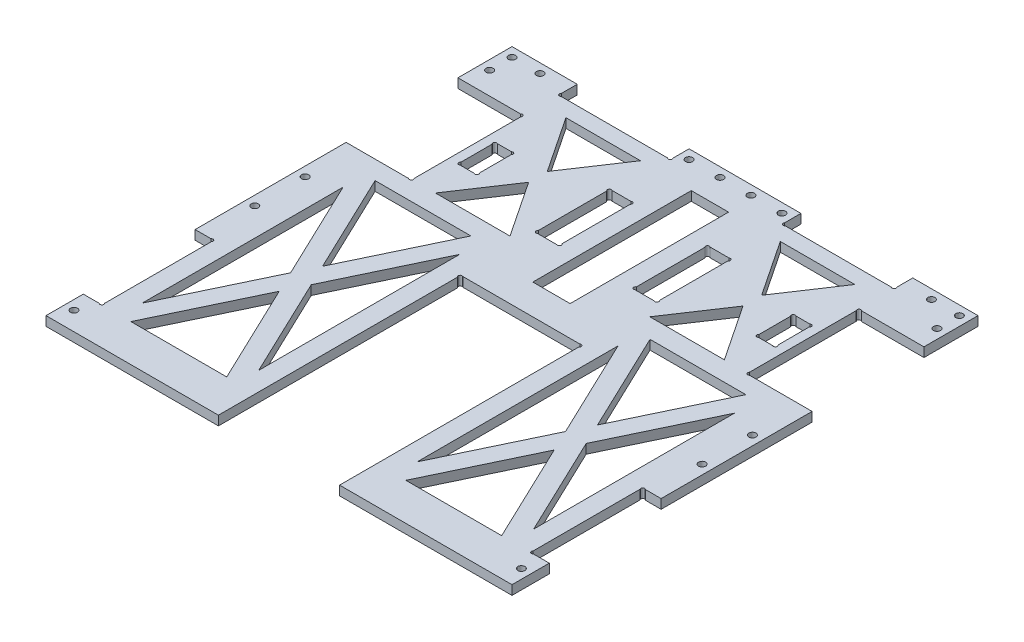
SolidWorks part; units mm, degrees
material "7050-T73510"
ref_plane "Front Plane" through (0, 0, 0) normal (0, 0, 1) x (1, 0, 0)
ref_plane "Top Plane" through (0, 0, 0) normal (0, 1, 0) x (1, 0, 0)
ref_plane "Right Plane" through (0, 0, 0) normal (1, 0, 0) x (0, 0, -1)
sketch "Sketch1" plane through (0, 0, 0) normal (0, 1, 0) x (1, 0, 0)
  line L0 (0, -55) -> (0, 55) construction
  line L1 (-158.75, -76.2) -> (158.75, -76.2)
  line L2 (-158.75, -76.2) -> (-158.75, 76.2)
  line L3 (-158.75, 76.2) -> (158.75, 76.2)
  line L4 (158.75, -76.2) -> (158.75, 76.2)
  line L5 (-158.75, -76.2) -> (158.75, 76.2) construction
  line L6 (-158.75, 76.2) -> (158.75, -76.2) construction
  line L7 (-158.75, -76.2) -> (-25.4, -76.2)
  line L8 (-158.75, -76.2) -> (-158.75, -241.3)
  line L9 (-158.75, -241.3) -> (-25.4, -241.3)
  line L10 (-25.4, -76.2) -> (-25.4, -241.3)
  line L11 (25.4, -76.2) -> (25.4, -241.3)
  line L12 (158.75, -241.3) -> (25.4, -241.3)
  line L13 (158.75, -76.2) -> (158.75, -241.3)
  line L14 (158.75, -76.2) -> (25.4, -76.2)
  line L15 (-41.275, -76.2) -> (-41.275, -241.3)
  line L16 (41.275, -76.2) -> (41.275, -241.3)
  point P0 (0, 0)
  dimension "D1" = 317.5
  dimension "D2" = 152.4
  dimension "D3" = 317.5
  dimension "D4" = 50.8
  dimension "D5" = 15.875
extrude "Boss-Extrude1" add sketch "Sketch1" along normal blind 6.35 contours L15 L1 L8 L9 | L14 L16 L12 L13 | L1 L7 L14 L4 L3 L2 region at (0, 0, 0) region at (-100.0125, 0, 158.75) region at (100.0125, 0, 158.75)
sketch "Sketch2" plane through (0, 6.35, 0) normal (0, 1, 0) x (1, 0, 0)
  line L0 (158.75, -241.3) -> (158.75, 76.2) construction
  line L1 (158.75, 39.37) -> (114.3, 39.37)
  line L2 (158.75, 39.37) -> (158.75, -36.83)
  line L3 (158.75, -36.83) -> (114.3, -36.83)
  line L4 (114.3, 39.37) -> (114.3, -36.83)
  line L5 (-158.75, 76.2) -> (158.75, 76.2) construction
  line L6 (158.75, -139.7) -> (146.05, -139.7)
  line L7 (158.75, -139.7) -> (158.75, -215.9)
  line L8 (158.75, -215.9) -> (146.05, -215.9)
  line L9 (146.05, -139.7) -> (146.05, -215.9)
  line L10 (0, -3.4925) -> (0, 3.4925) construction
  line L11 (-158.75, -215.9) -> (-146.05, -215.9)
  line L12 (-146.05, -139.7) -> (-146.05, -215.9)
  line L13 (-158.75, -139.7) -> (-146.05, -139.7)
  line L14 (-158.75, -139.7) -> (-158.75, -215.9)
  line L15 (-158.75, -36.83) -> (-114.3, -36.83)
  line L16 (-114.3, 39.37) -> (-114.3, -36.83)
  line L17 (-158.75, 39.37) -> (-114.3, 39.37)
  line L18 (-158.75, 39.37) -> (-158.75, -36.83)
  line L19 (-114.3, 63.5) -> (-38.1, 63.5)
  line L20 (114.3, 76.2) -> (38.1, 76.2)
  line L21 (114.3, 76.2) -> (114.3, 63.5)
  line L22 (114.3, 63.5) -> (38.1, 63.5)
  line L23 (38.1, 76.2) -> (38.1, 63.5)
  line L24 (-38.1, 76.2) -> (-38.1, 63.5)
  line L25 (-114.3, 76.2) -> (-38.1, 76.2)
  line L26 (-114.3, 76.2) -> (-114.3, 63.5)
  point P30 (0, 0)
  dimension "D1" = 44.45
  dimension "D2" = 12.7
  dimension "D3" = 76.2
  dimension "D4" = 76.2
  dimension "D5" = 36.83
  dimension "D6" = 215.9
  dimension "D7" = 76.2
  dimension "D8" = 12.7
  dimension "D9" = 76.2
extrude "Cut-Extrude1" cut sketch "Sketch2" against normal through all
sketch "Sketch4" plane through (0, 6.35, 0) normal (0, 1, 0) x (1, 0, 0)
  line L0 (41.275, -76.2) -> (41.275, -241.3) construction
  line L1 (53.975, -215.9) -> (133.35, -215.9)
  line L2 (53.975, -215.9) -> (53.975, -49.53)
  line L3 (53.975, -49.53) -> (133.35, -49.53)
  line L4 (133.35, -215.9) -> (133.35, -49.53)
  line L5 (146.05, -139.7) -> (146.05, -215.9) construction
  line L6 (158.75, -241.3) -> (41.275, -241.3) construction
  line L7 (53.975, -215.9) -> (133.35, -49.53) construction
  line L8 (53.975, -49.53) -> (133.35, -215.9) construction
  line L9 (133.35, -201.1532) -> (61.0107, -49.53)
  line L10 (126.3143, -215.9) -> (53.975, -64.2768)
  line L11 (53.975, -201.1532) -> (126.3143, -49.53)
  line L12 (61.0107, -215.9) -> (133.35, -64.2768)
  line L13 (114.3, -36.83) -> (158.75, -36.83) construction
  line L14 (0, -3.4925) -> (0, 3.4925) construction
  line L15 (-53.975, -201.1532) -> (-126.3143, -49.53)
  line L16 (-126.3143, -215.9) -> (-53.975, -64.2768)
  line L17 (-133.35, -201.1532) -> (-61.0107, -49.53)
  line L18 (-61.0107, -215.9) -> (-133.35, -64.2768)
  line L19 (-53.975, -49.53) -> (-133.35, -49.53)
  line L20 (-133.35, -215.9) -> (-133.35, -49.53)
  line L21 (-53.975, -215.9) -> (-133.35, -215.9)
  line L22 (-53.975, -215.9) -> (-53.975, -49.53)
  point P18 (116.9135, -166.7022)
  dimension "D1" = 12.7
  dimension "D2" = 12.7
  dimension "D3" = 25.4
  dimension "D4" = 12.7
  dimension "D5" = 12.7
extrude "Cut-Extrude3" cut sketch "Sketch4" against normal through all contours L12 L9 L4 | L12 L1 L10 | L2 L11 L10 | L9 L11 L3 | L21 L18 L16 | L20 L17 L18 | L17 L19 L15 | L15 L22 L16 region at (93.6625, 6.35, 193.0873) region at (64.8589, 6.35, 132.715) region at (122.4661, 6.35, 132.715) region at (93.6625, 6.35, 72.3427) region at (-64.8589, 6.35, 132.715) region at (-93.6625, 6.35, 72.3427) region at (-93.6625, 6.35, 193.0873) region at (-122.4661, 6.35, 132.715)
sketch "Sketch3" plane through (0, 6.35, 0) normal (0, 1, 0) x (1, 0, 0)
  line L0 (-41.275, -76.2) -> (41.275, -76.2) construction
  line L1 (-41.275, -25.4) -> (-25.4, -25.4)
  line L2 (-41.275, -25.4) -> (-41.275, 25.4)
  line L3 (-41.275, 25.4) -> (-25.4, 25.4)
  line L4 (-25.4, -25.4) -> (-25.4, 25.4)
  line L5 (0, -3.4925) -> (0, 3.4925) construction
  line L6 (41.275, 25.4) -> (25.4, 25.4)
  line L7 (25.4, -25.4) -> (25.4, 25.4)
  line L8 (41.275, -25.4) -> (25.4, -25.4)
  line L9 (41.275, -25.4) -> (41.275, 25.4)
  line L10 (114.3, 39.37) -> (114.3, -36.83) construction
  line L11 (95.25, 13.97) -> (107.95, 13.97)
  line L12 (95.25, 13.97) -> (95.25, -11.43)
  line L13 (95.25, -11.43) -> (107.95, -11.43)
  line L14 (107.95, 13.97) -> (107.95, -11.43)
  line L15 (38.1, 63.5) -> (114.3, 63.5) construction
  line L16 (-95.25, -11.43) -> (-107.95, -11.43)
  line L17 (-107.95, 13.97) -> (-107.95, -11.43)
  line L18 (-95.25, 13.97) -> (-107.95, 13.97)
  line L19 (-95.25, 13.97) -> (-95.25, -11.43)
  dimension "D1" = 50.8
  dimension "D2" = 15.875
  dimension "D3" = 50.8
  dimension "D4" = 50.8
  dimension "D5" = 25.4
  dimension "D6" = 12.7
  dimension "D7" = 6.35
  dimension "D8" = 49.53
extrude "Cut-Extrude2" cut sketch "Sketch3" against normal through all
sketch "Sketch6" plane through (0, 6.35, 0) normal (0, 1, 0) x (1, 0, 0)
  line L0 (-25.4, -25.4) -> (-25.4, 25.4) construction
  line L1 (-19.05, 63.5) -> (19.05, 63.5)
  line L2 (-19.05, 63.5) -> (-19.05, -63.5)
  line L3 (-19.05, -63.5) -> (19.05, -63.5)
  line L4 (19.05, 63.5) -> (19.05, -63.5)
  line L5 (25.4, 25.4) -> (25.4, -25.4) construction
  line L6 (-38.1, 76.2) -> (38.1, 76.2) construction
  line L7 (-41.275, -76.2) -> (41.275, -76.2) construction
  line L8 (-19.05, -63.5) -> (19.05, 63.5) construction
  line L9 (19.05, -63.5) -> (-19.05, 63.5) construction
  line L10 (12.4204, -63.5) -> (-19.05, 41.4014)
  line L11 (-12.4204, 63.5) -> (19.05, -41.4014)
  line L12 (-19.05, -41.4014) -> (12.4204, 63.5)
  line L13 (19.05, 41.4014) -> (-12.4204, -63.5)
  dimension "D1" = 6.35
  dimension "D2" = 6.35
  dimension "D3" = 12.7
  dimension "D4" = 12.7
  dimension "D5" = 12.7
  dimension "D6" = 12.7
extrude "Cut-Extrude5" [suppressed] cut sketch "Sketch6" against normal through all contours L10 L13 L3 | L4 L13 L11 | L2 L12 L10 | L11 L12 L1
sketch "Sketch7" plane through (0, 6.35, 0) normal (0, 1, 0) x (1, 0, 0)
  line L0 (158.75, -139.7) -> (146.05, -139.7) construction
  line L1 (158.75, -139.7) -> (158.75, -36.83) construction
  line L2 (0, -3.4925) -> (0, 3.4925) construction
  line L3 (158.75, -241.3) -> (41.275, -241.3) construction
  line L4 (-38.1, 76.2) -> (-38.1, 63.5) construction
  line L5 (114.3, 76.2) -> (158.75, 76.2) construction
  line L6 (-38.1, 76.2) -> (38.1, 76.2) construction
  circle A0 centre (152.4, -105.41) radius 2.413
  circle A1 centre (152.4, -71.12) radius 2.413
  circle A8 centre (152.4, -228.6) radius 2.413
  circle A9 centre (152.4, 69.85) radius 2.413
  circle A10 centre (133.35, 69.85) radius 2.413
  circle A12 centre (152.4, 54.61) radius 2.413
  circle A19 centre (-152.4, -228.6) radius 2.413
  circle A20 centre (-31.75, 69.85) radius 2.413
  circle A21 centre (-10.668, 69.85) radius 2.413
  circle A22 centre (10.414, 69.85) radius 2.413
  circle A23 centre (31.496, 69.85) radius 2.413
  circle A24 centre (-152.4, 54.61) radius 2.413
  circle A25 centre (-133.35, 69.85) radius 2.413
  circle A26 centre (-152.4, 69.85) radius 2.413
  circle A27 centre (-152.4, -71.12) radius 2.413
  circle A28 centre (-152.4, -105.41) radius 2.413
  dimension "D1" = 4.826
  dimension "D3" = 6.35
  dimension "D5" = 12.7
  dimension "D6" = 6.35
  dimension "D9" = 4.826
  dimension "D2" = 34.29
  dimension "D8" = 2
  dimension "D10" = 6.35
  dimension "D11" = 6.35
  dimension "D4" = 2
  dimension "D7" = 2
  dimension "D12" = 4
extrude "Cut-Extrude6" cut sketch "Sketch7" against normal through all
sketch "Sketch5" plane through (0, 6.35, 0) normal (0, 1, 0) x (1, 0, 0)
  line L0 (0, -3.4925) -> (0, 3.4925) construction
  line L2 (-38.1, 76.2) -> (38.1, 76.2) construction
  line L3 (41.275, -25.4) -> (41.275, 25.4) construction
  line L4 (114.3, 63.5) -> (38.1, 63.5) construction
  circle A0 centre (12.7, 63.5) radius 6.35
  circle A1 centre (12.7, 50.8) radius 6.35
  circle A2 centre (12.7, 38.1) radius 6.35
  circle A3 centre (12.7, 25.4) radius 6.35
  circle A4 centre (12.7, 12.7) radius 6.35
  circle A11 centre (0, 50.8) radius 6.35
  circle A12 centre (0, 38.1) radius 6.35
  circle A13 centre (0, 25.4) radius 6.35
  circle A14 centre (0, 12.7) radius 6.35
  circle A21 centre (-12.7, 50.8) radius 6.35
  circle A22 centre (-12.7, 38.1) radius 6.35
  circle A23 centre (-12.7, 25.4) radius 6.35
  circle A24 centre (-12.7, 12.7) radius 6.35
  circle A31 centre (0, 63.5) radius 6.35
  circle A32 centre (-12.7, 63.5) radius 6.35
  circle A33 centre (53.975, 50.8) radius 3.175
  circle A34 centre (66.675, 50.8) radius 3.175
  circle A35 centre (79.375, 50.8) radius 3.175
  circle A36 centre (66.675, 38.1) radius 3.175
  circle A37 centre (79.375, 38.1) radius 3.175
  circle A38 centre (66.675, 25.4) radius 3.175
  circle A39 centre (79.375, 25.4) radius 3.175
  circle A40 centre (66.675, 12.7) radius 3.175
  circle A41 centre (79.375, 12.7) radius 3.175
  circle A42 centre (66.675, 0) radius 3.175
  circle A43 centre (79.375, 0) radius 3.175
  circle A44 centre (66.675, -12.7) radius 3.175
  circle A45 centre (79.375, -12.7) radius 3.175
  circle A46 centre (66.675, -25.4) radius 3.175
  circle A47 centre (79.375, -25.4) radius 3.175
  circle A48 centre (66.675, -38.1) radius 3.175
  circle A49 centre (79.375, -38.1) radius 3.175
  circle A50 centre (53.975, 38.1) radius 3.175
  circle A51 centre (53.975, 25.4) radius 3.175
  circle A52 centre (53.975, 12.7) radius 3.175
  circle A53 centre (53.975, 0) radius 3.175
  circle A54 centre (53.975, -12.7) radius 3.175
  circle A55 centre (53.975, -25.4) radius 3.175
  circle A56 centre (53.975, -38.1) radius 3.175
  circle A57 centre (-53.975, -38.1) radius 3.175
  circle A58 centre (-53.975, -25.4) radius 3.175
  circle A59 centre (-53.975, -12.7) radius 3.175
  circle A60 centre (-53.975, 0) radius 3.175
  circle A61 centre (-53.975, 12.7) radius 3.175
  circle A62 centre (-53.975, 25.4) radius 3.175
  circle A63 centre (-53.975, 38.1) radius 3.175
  circle A64 centre (-79.375, -38.1) radius 3.175
  circle A65 centre (-66.675, -38.1) radius 3.175
  circle A66 centre (-79.375, -25.4) radius 3.175
  circle A67 centre (-66.675, -25.4) radius 3.175
  circle A68 centre (-79.375, -12.7) radius 3.175
  circle A69 centre (-66.675, -12.7) radius 3.175
  circle A70 centre (-79.375, 0) radius 3.175
  circle A71 centre (-66.675, 0) radius 3.175
  circle A72 centre (-79.375, 12.7) radius 3.175
  circle A73 centre (-66.675, 12.7) radius 3.175
  circle A74 centre (-79.375, 25.4) radius 3.175
  circle A75 centre (-66.675, 25.4) radius 3.175
  circle A76 centre (-79.375, 38.1) radius 3.175
  circle A77 centre (-66.675, 38.1) radius 3.175
  circle A78 centre (-79.375, 50.8) radius 3.175
  circle A79 centre (-66.675, 50.8) radius 3.175
  circle A80 centre (-53.975, 50.8) radius 3.175
  dimension "D1" = 12.7
  dimension "D6" = 6.35
  dimension "D2" = 12.7
  dimension "D3" = 12.7
  dimension "D7" = 12.7
  dimension "D8" = 12.7
  dimension "D4" = 5
  dimension "D5" = 3
  dimension "D9" = 3
  dimension "D10" = 8
sketch "Sketch10" plane through (0, 6.35, 0) normal (0, 1, 0) x (1, 0, 0)
  line L0 (0, -3.4925) -> (0, 3.4925) construction
  circle A0 centre (-146.9728, -215.0274) radius 1.27
  circle A1 centre (-147.0286, -140.5095) radius 1.27
  circle A2 centre (-115.2095, -35.9436) radius 1.27
  circle A3 centre (-115.2533, 38.5309) radius 1.27
  circle A4 centre (-113.4221, 64.4177) radius 1.27
  circle A5 centre (-39.0797, 64.3081) radius 1.27
  circle A8 centre (-107.1935, 12.9499) radius 1.27
  circle A9 centre (-96.0928, 13.02) radius 1.27
  circle A10 centre (-107.2327, -10.382) radius 1.27
  circle A11 centre (-96.0288, -10.4268) radius 1.27
  circle A12 centre (-40.5811, 24.3363) radius 1.27
  circle A13 centre (-26.2184, 24.4288) radius 1.27
  circle A15 centre (-40.5236, -24.3761) radius 1.27
  circle A16 centre (-25.9957, -24.2784) radius 1.27
  circle A17 centre (-40.5722, -77.2578) radius 1.27
  circle A18 centre (40.5722, -77.2578) radius 1.27
  circle A19 centre (25.9957, -24.2784) radius 1.27
  circle A20 centre (40.5236, -24.3761) radius 1.27
  circle A21 centre (26.2184, 24.4288) radius 1.27
  circle A22 centre (40.5811, 24.3363) radius 1.27
  circle A23 centre (96.0288, -10.4268) radius 1.27
  circle A24 centre (107.2327, -10.382) radius 1.27
  circle A25 centre (96.0928, 13.02) radius 1.27
  circle A26 centre (107.1935, 12.9499) radius 1.27
  circle A27 centre (39.0797, 64.3081) radius 1.27
  circle A28 centre (113.4221, 64.4177) radius 1.27
  circle A29 centre (115.2533, 38.5309) radius 1.27
  circle A30 centre (115.2095, -35.9436) radius 1.27
  circle A31 centre (147.0286, -140.5095) radius 1.27
  circle A32 centre (146.9728, -215.0274) radius 1.27
  point P51 (0, 0)
extrude "Cut-Extrude7" cut sketch "Sketch10" against normal through all
sketch "Sketch12" plane through (0, 6.35, 0) normal (0, 1, 0) x (1, 0, 0)
  line L0 (-98.425, 52.6142) -> (-47.625, 52.6142)
  line L1 (-47.625, 52.6142) -> (-73.025, 14.5142)
  line L2 (-73.025, 14.5142) -> (-98.425, 52.6142)
  line L3 (-94.4842, 8.1642) -> (-61.9728, 8.1642) construction
  line L4 (-114.3, 39.37) -> (-114.3, -36.83) construction
  line L5 (-47.625, -36.2858) -> (-73.025, 1.8142)
  line L6 (-98.425, -36.2858) -> (-47.625, -36.2858)
  line L7 (-73.025, 1.8142) -> (-98.425, -36.2858)
  line L8 (0, -3.4925) -> (0, 3.4925) construction
  line L9 (94.4842, 8.1642) -> (61.9728, 8.1642) construction
  line L10 (73.025, 1.8142) -> (98.425, -36.2858)
  line L11 (98.425, -36.2858) -> (47.625, -36.2858)
  line L12 (47.625, -36.2858) -> (73.025, 1.8142)
  line L13 (73.025, 14.5142) -> (98.425, 52.6142)
  line L14 (47.625, 52.6142) -> (73.025, 14.5142)
  line L15 (98.425, 52.6142) -> (47.625, 52.6142)
  line L23 (-12.7, -55.6542) -> (12.7, -55.6542)
  line L24 (-12.7, -55.6542) -> (-12.7, 52.2958)
  line L25 (-12.7, 52.2958) -> (12.7, 52.2958)
  line L26 (12.7, -55.6542) -> (12.7, 52.2958)
  point P6 (-73.025, 52.6142)
  point P25 (0, -55.6542)
  dimension "D1" = 6.35
  dimension "D2" = 44.45
  dimension "D3" = 50.8
  dimension "D4" = 41.275
  dimension "D5" = 25.4
  dimension "D6" = 107.95
extrude "Cut-Extrude9" cut sketch "Sketch12" against normal through all
